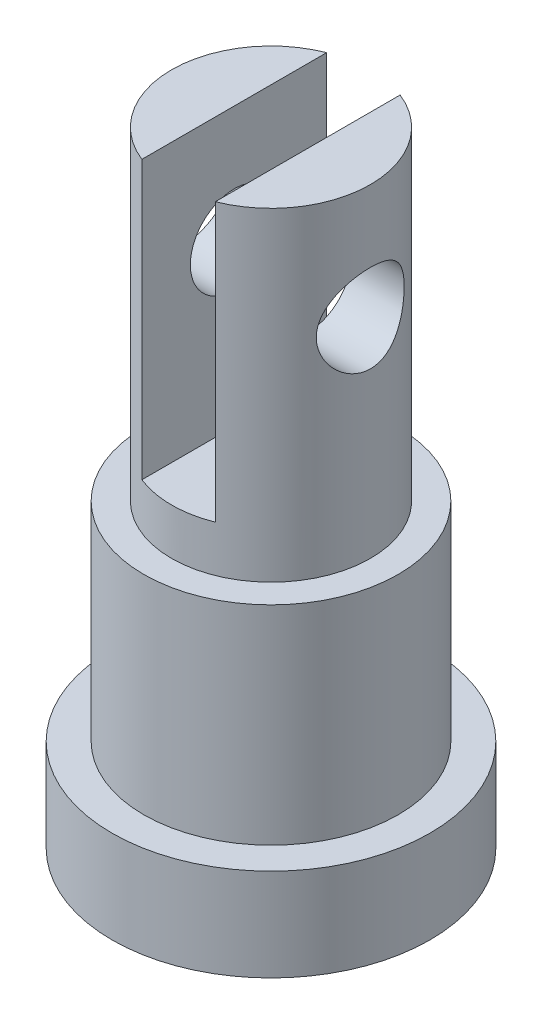
SolidWorks part; units mm, degrees
material "ABS"
ref_plane "Front Plane" through (0, 0, 0) normal (0, 0, 1) x (1, 0, 0)
ref_plane "Top Plane" through (0, 0, 0) normal (0, 1, 0) x (1, 0, 0)
ref_plane "Right Plane" through (0, 0, 0) normal (1, 0, 0) x (0, 0, -1)
sketch "Sketch1" plane through (0, 0, 0) normal (0, 1, 0) x (1, 0, 0)
  circle A0 centre (0, 0) radius 6.875
  dimension "D1" = 13.75
extrude "Boss-Extrude1" add sketch "Sketch1" along normal blind 4
sketch "Sketch2" plane through (0, 4, 0) normal (0, 1, 0) x (1, 0, 0)
  circle A2 centre (0, 0) radius 5.5
  point P0 (0, 0)
  dimension "D1" = 11
extrude "Boss-Extrude2" add sketch "Sketch2" along normal blind 9
sketch "Sketch3" plane through (0, 13, 0) normal (0, 1, 0) x (1, 0, 0)
  circle A0 centre (0, 0) radius 4.3
  dimension "D1" = 8.6
extrude "Boss-Extrude3" add sketch "Sketch3" along normal blind 14
sketch "Sketch4" plane through (0, 27, 0) normal (0, 1, 0) x (1, 0, 0)
  line L1 (-1.5875, 4.3) -> (1.5875, 4.3)
  line L2 (-1.5875, 4.3) -> (-1.5875, -4.3)
  line L3 (-1.5875, -4.3) -> (1.5875, -4.3)
  line L4 (1.5875, 4.3) -> (1.5875, -4.3)
  line L5 (-1.5875, 4.3) -> (1.5875, -4.3) construction
  line L6 (-1.5875, -4.3) -> (1.5875, 4.3) construction
  point P0 (0, 0)
  dimension "D1" = 8.6
  dimension "D2" = 3.175
extrude "Cut-Extrude1" cut sketch "Sketch4" against normal blind 12
sketch "Sketch5" plane through (1.5875, 0, 0) normal (-1, 0, 0) x (0, 0, 1)
  line L0 (3.9962, 15) -> (-3.9962, 15) construction
  line L1 (3.9962, 27) -> (-3.9962, 27) construction
  line L2 (3.9962, 15) -> (-3.9962, 15)
  line L3 (3.9962, 27) -> (-3.9962, 27)
  line L4 (0, 15) -> (0, 22) construction
  circle A0 centre (0, 22) radius 1.9
  dimension "D2" = 3.8
  dimension "D1" = 7
extrude "Cut-Extrude2" cut sketch "Sketch5" against normal through all both and the other way through all contours A0
equation "\"prop-dist\"= 80mm"
equation "\"prop-hole-depth\"= 9mm"
equation "\"prop-hole-diameter\"= 11mm"
equation "\"rivet-extension\" = 12mm"
equation "\"rivet-hole-extension\"= 7mm"
equation "\"rivet-hole-diameter\"= 3.8mm"
equation "\"ski-length\"= 100mm"
equation "\"th\"= 0.125in'material thickness"
equation "\"ski-height\"= 30mm"
equation "\"ski-curve-gap\"= 60mm"
equation "\"ski-curve-height\"= \"rivet-hole-extension\""
equation "\"min-width\"= 4mm"
equation "\"prop-hole-diameter-small\"= 8.6mm"
equation "\"D1@Sketch1\"=\"prop-hole-diameter\"*1.25"
equation "\"D1@Sketch2\"=\"prop-hole-diameter\""
equation "\"D1@Boss-Extrude2\"=\"prop-hole-depth\""
equation "\"D1@Sketch3\"=\"prop-hole-diameter-small\""
equation "\"D1@Boss-Extrude3\"=\"rivet-extension\"+2mm"
equation "\"D1@Sketch4\"=\"prop-hole-diameter-small\""
equation "\"D2@Sketch4\"=\"th\""
equation "\"D1@Cut-Extrude1\"=\"rivet-extension\""
equation "\"D1@Sketch5\"=\"rivet-hole-extension\""
equation "\"D2@Sketch5\"=\"rivet-hole-diameter\""
